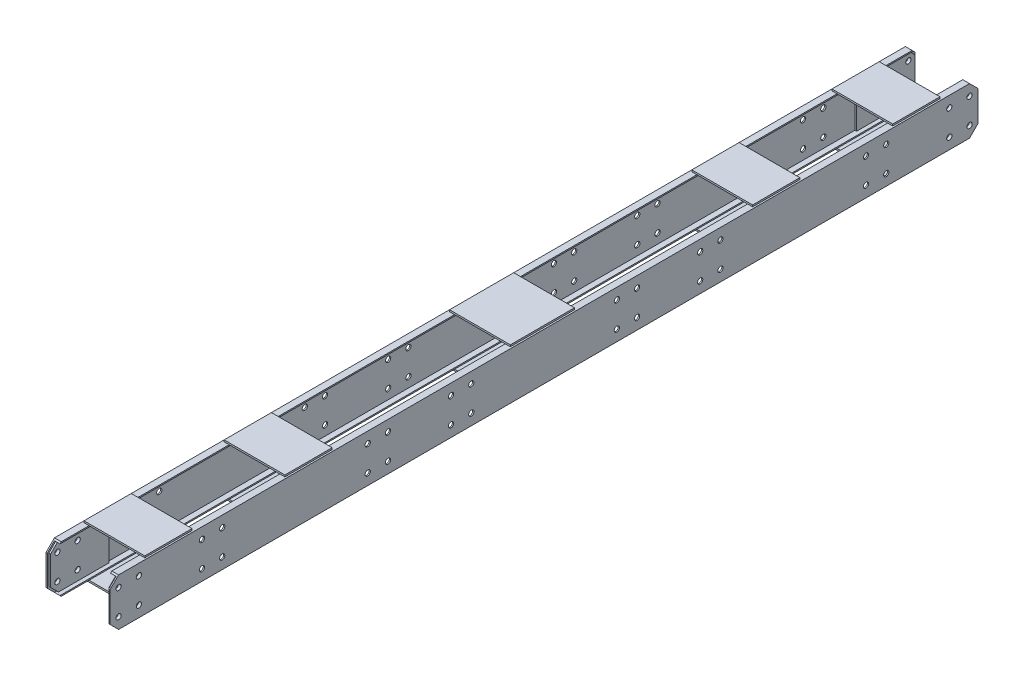
SolidWorks part; units mm, degrees
ref_plane "前视基准面" through (0, 0, 0) normal (0, 0, 1) x (1, 0, 0)
ref_plane "上视基准面" through (0, 0, 0) normal (0, 1, 0) x (1, 0, 0)
ref_plane "右视基准面" through (0, 0, 0) normal (1, 0, 0) x (0, 0, -1)
sketch "草图1" plane through (0, 0, 0) normal (0, 0, 1) x (1, 0, 0)
  line L0 (-1000, 0) -> (49000, 0) construction
  line L1 (-190, 140) -> (-150, 140)
  line L2 (-190, 140) -> (-190, -140)
  line L3 (-190, -140) -> (-150, -140)
  line L4 (-150, 140) -> (-150, -140)
  line L5 (-182.5, 132.5) -> (-150, 132.5)
  line L6 (-182.5, 132.5) -> (-182.5, -132.5)
  line L7 (-182.5, -132.5) -> (-150, -132.5)
  line L8 (-150, 132.5) -> (-150, -132.5)
  line L9 (0, -1000) -> (0, 49000) construction
  dimension "D1" = 7.5
  dimension "D2" = 7.5
  dimension "D3" = 7.5
  dimension "D4" = 280
  dimension "D5" = 140
  dimension "D6" = 40
  dimension "D7" = 190
extrude "拉伸1" add sketch "草图1" along normal blind 2570 contours L7 L6 L5 L4 L1 L2 L3 region at (-170, 137.1716, 0)
sketch "草图2" plane through (0, 140, 0) normal (0, 1, 0) x (1, 0, 0)
  line L0 (-190, -2570) -> (-190, 0) construction
  line L1 (-180, -215) -> (180, -215)
  line L2 (-180, -215) -> (-180, -495)
  line L3 (-180, -495) -> (180, -495)
  line L4 (180, -215) -> (180, -495)
  line L5 (-190, 0) -> (-150, 0) construction
  line L6 (-180, -1045) -> (180, -1045)
  line L7 (-180, -1045) -> (-180, -1325)
  line L8 (180, -1045) -> (180, -1325)
  line L9 (-180, -1325) -> (180, -1325)
  line L10 (-180, -215) -> (-180, -1045) construction
  line L12 (-180, -2380) -> (180, -2380)
  line L13 (-180, -2380) -> (-180, -2570)
  line L14 (-180, -2570) -> (180, -2570)
  line L15 (180, -2380) -> (180, -2570)
  dimension "D1" = 280
  dimension "D2" = 360
  dimension "D3" = 10
  dimension "D4" = 215
  dimension "D5" = 830
  dimension "D6" = 190
  dimension "D7" = 360
  dimension "D8" = 10
  dimension "D9" = 1055
extrude "拉伸2" add sketch "草图2" along normal blind 10
mirror "镜向2" about plane through (0, 0, 0) normal (1, 0, 0) of bodies 102
mirror "镜向3" about plane through (0, 0, 0) normal (0, 1, 0) of bodies 105
sketch "草图5" plane through (-190, 0, 0) normal (-1, 0, 0) x (0, 0, 1)
  line L0 (-1000, 0) -> (49000, 0) construction
  line L1 (1285, -860) -> (1285, 49140) construction
  line L2 (2570, 140) -> (0, 140) construction
  line L3 (0, 140) -> (0, -140) construction
  line L4 (50, 75) -> (170, 75) construction
  line L5 (50, 75) -> (50, -75) construction
  line L6 (50, 75) -> (543.5, 75) construction
  line L7 (663.5, 75) -> (1645.5, 75) construction
  line L8 (1645.5, 75) -> (2139, 75) construction
  line L10 (50, 140) -> (0, 90)
  line L11 (0, 90) -> (0, 140)
  line L12 (0, 140) -> (50, 140)
  line L13 (0, -90) -> (50, -140)
  line L14 (2570, -140) -> (0, -140) construction
  line L15 (50, -140) -> (0, -140)
  line L16 (0, -140) -> (0, -90)
  circle A0 centre (50, 75) radius 15.5
  circle A1 centre (170, 75) radius 15.5
  circle A2 centre (50, -75) radius 15.5
  circle A3 centre (170, -75) radius 15.5
  circle A4 centre (543.5, 75) radius 15.5
  circle A5 centre (663.5, 75) radius 15.5
  circle A6 centre (663.5, -75) radius 15.5
  circle A7 centre (543.5, -75) radius 15.5
  circle A8 centre (1645.5, 75) radius 15.5
  circle A9 centre (1525.5, 75) radius 15.5
  circle A10 centre (1525.5, -75) radius 15.5
  circle A11 centre (1645.5, -75) radius 15.5
  circle A12 centre (2139, 75) radius 15.5
  circle A13 centre (2019, 75) radius 15.5
  circle A14 centre (2019, -75) radius 15.5
  circle A15 centre (2139, -75) radius 15.5
  point P8 (1285, 140)
  dimension "D1" = 31
  dimension "D2" = 50
  dimension "D3" = 75
  dimension "D4" = 120
  dimension "D5" = 150
  dimension "D6" = 493.5
  dimension "D7" = 982
  dimension "D8" = 493.5
  dimension "D9" = 50
  dimension "D10" = 50
  dimension "D11" = 50
  dimension "D12" = 50
extrude "拉伸3" cut sketch "草图5" against normal through all
sketch "草图10" plane through (182.5, 0, 0) normal (-1, 0, 0) x (0, 0, 1)
  line L0 (-1000, 0) -> (49000, 0) construction
  line L1 (0, 90) -> (0, -90) construction
  line L2 (10, 85.8579) -> (10, -85.8579)
  line L3 (10, -85.8579) -> (56.6421, -132.5)
  line L4 (2570, -132.5) -> (42.5, -132.5) construction
  line L5 (56.6421, -132.5) -> (356.6421, -132.5)
  line L7 (42.5, -132.5) -> (0, -90) construction
  line L8 (356.6421, -132.5) -> (356.6421, 132.5)
  line L9 (56.6421, 132.5) -> (356.6421, 132.5)
  line L10 (10, 85.8579) -> (56.6421, 132.5)
  point P5 (0, 0)
  point P12 (356.6421, 0)
  point P17 (10, 0)
  dimension "D1" = 10
  dimension "D2" = 10
  dimension "D3" = 300
extrude "拉伸8" add sketch "草图10" along normal blind 10
mirror "镜向6" about plane through (0, 0, 0) normal (1, 0, 0) of "拉伸8"
extrude "拉伸9" cut sketch "草图5<6>" against normal through all
sketch "草图5<6>" plane through (-190, 0, 0) normal (-1, 0, 0) x (0, 0, 1) same geometry as "草图5"
mirror "镜向7" about plane through (0, 0, 2570) normal (0, 0, 1) of bodies 117
sketch "草图11" plane through (-190, 0, 0) normal (-1, 0, 0) x (0, 0, 1)
  line L0 (50, 75) -> (5090, 75) construction
